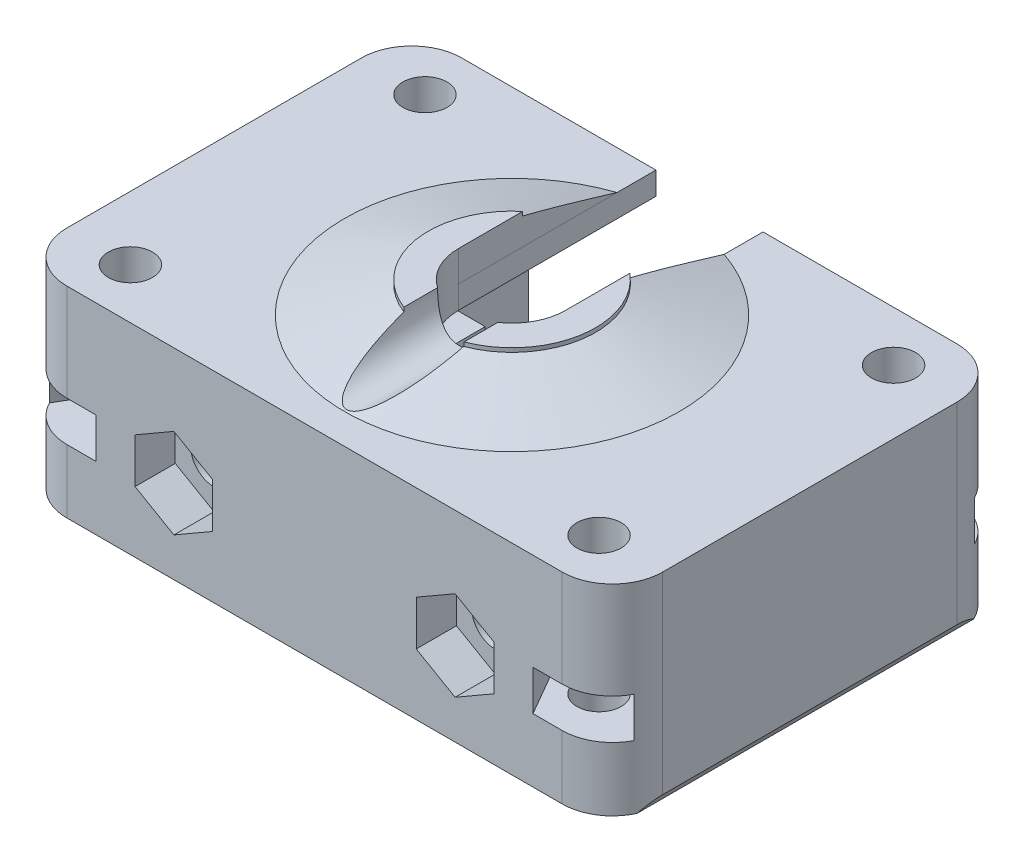
SolidWorks part; units mm, degrees
ref_plane "Plano frontal" through (0, 0, 0) normal (0, 0, 1) x (1, 0, 0)
ref_plane "Plano superior" through (0, 0, 0) normal (0, 1, 0) x (1, 0, 0)
ref_plane "Plano direito" through (0, 0, 0) normal (1, 0, 0) x (0, 0, -1)
sketch "Esboço1" plane through (0, 0, 0) normal (0, 1, 0) x (1, 0, 0)
  line L0 (-18.7321, -12.0975) -> (-21.3284, -13.8284) construction
  line L1 (-18.5, -15) -> (18.5, -15)
  line L2 (-22.5, -11) -> (-22.5, 11)
  line L3 (-18.5, 15) -> (18.5, 15)
  line L4 (22.5, -11) -> (22.5, 11)
  line L5 (-22.5, -15) -> (22.5, 15) construction
  line L6 (-22.5, 15) -> (22.5, -15) construction
  line L7 (-17.5, -11) -> (17.5, -11) construction
  line L8 (17.5, -11) -> (17.5, 11) construction
  line L9 (17.5, 11) -> (-17.5, 11) construction
  line L10 (-17.5, 11) -> (-17.5, -11) construction
  line L11 (0, -11) -> (0, 0) construction
  line L12 (-17.5, 0) -> (0, 0) construction
  arc A0 (-18.5, -15) -> (-22.5, -11) centre (-18.5, -11) cw
  arc A1 (18.5, -15) -> (22.5, -11) centre (18.5, -11) ccw
  arc A2 (18.5, 15) -> (22.5, 11) centre (18.5, 11) cw
  arc A3 (-22.5, 11) -> (-18.5, 15) centre (-18.5, 11) cw
  circle A8 centre (-17.5, -11) radius 1.65
  circle A9 centre (-17.5, 11) radius 1.65
  circle A10 centre (17.5, -11) radius 1.65
  circle A11 centre (17.5, 11) radius 1.65
  point P0 (0, 0)
  dimension "D3" = 4
  dimension "D4" = 35
  dimension "D6" = 3.3
  dimension "D1" = 45
  dimension "D2" = 30
  dimension "D5" = 22
extrude "Ressalto-extrusão1" add sketch "Esboço1" along normal blind 17
sketch "Esboço3" plane through (0, 0, 0) normal (0, -1, 0) x (1, 0, 0)
  line L0 (-4, -15) -> (4, -15)
  line L1 (4, -15) -> (4, 0)
  line L2 (-4, -15) -> (-4, 0)
  line L3 (18.5, -15) -> (-18.5, -15) construction
  line L4 (0, 0) -> (0, -15) construction
  arc A0 (-4, 0) -> (4, 0) centre (0, 0) cw
  dimension "D2" = 4
extrude "Corte-extrusão2" cut sketch "Esboço3" against normal through all
sketch "Esboço4" plane through (0, 0, 0) normal (0, -1, 0) x (1, 0, 0)
  line L0 (-8.48, -15) -> (-8.48, 0)
  line L1 (-6.25, -15) -> (-6.25, 0)
  line L2 (6.25, -15) -> (6.25, 0)
  line L3 (8.48, -15) -> (8.48, 0)
  line L4 (-8.48, -15) -> (8.48, -15)
  line L5 (0, -15) -> (0, 0) construction
  line L7 (18.5, -15) -> (4, -15) construction
  arc A0 (-8.48, 0) -> (8.48, 0) centre (0, 0) cw
  arc A1 (-6.25, 0) -> (6.25, 0) centre (0, 0) cw
  line M44 (-4, -15) -> (-4, 0)
  arc M45 (-4, 0) -> (4, 0) centre (0, 0) cw
  line M46 (4, 0) -> (4, -15)
  line M47 (4, -15) -> (18.5, -15)
  line M55 (-18.5, -15) -> (-4, -15)
  dimension "D1" = 8.48
  dimension "D2" = 6.25
extrude "Corte-extrusão3" cut sketch "Esboço4" against normal blind 5.5 contours A0 L3 L4 L0
extrude "Corte-extrusão4" cut sketch "Esboço4<3>" against normal blind 15.3 contours A1 L1 L2 M55 M44 M45 M46 M47 region at (-6.0035, 0, -7.5)
sketch "Esboço4<3>" plane through (0, 0, 0) normal (0, -1, 0) x (1, 0, 0) same geometry as "Esboço4"
sketch "Esboço5" plane through (0, 15.3, 0) normal (0, -1, 0) x (1, 0, 0)
  line L0 (-8.48, -15) -> (-8.48, 0.0526)
  line L1 (-6.25, -15) -> (-6.25, 0.0526)
  line L2 (6.25, -15) -> (6.25, 0.0526)
  line L3 (8.48, -15) -> (8.48, 0.0526)
  line L4 (-8.48, -15) -> (8.48, -15)
  line L5 (0, -15) -> (0, 0) construction
  line L6 (-6.25, -15) -> (-4, -15) construction
  line L7 (-6.25, 0) -> (-6.25, -15) construction
  arc A0 (-8.48, 0.0526) -> (8.48, 0.0526) centre (0, 0.0526) cw
  arc A1 (-6.25, 0.0526) -> (6.25, 0.0526) centre (0, 0.0526) cw
  dimension "D1" = 8.48
  dimension "D2" = 6.25
  dimension "D3" = 15.0526
extrude "Corte-extrusão5" cut sketch "Esboço5" along normal blind 4.3 contours L0 A0 L3 L4
sketch "Esboço6" plane through (0, 17, 0) normal (0, 1, 0) x (1, 0, 0)
  line L0 (-14, 0) -> (-14, 8.3)
  line L1 (14, 0) -> (14, 8.3)
  line L2 (14, 8.3) -> (-14, 8.3)
  line L3 (-4, 0) -> (-4, 8.3)
  line L4 (4, 0) -> (4, 8.3)
  circle A0 centre (0, 0) radius 4
  circle A1 centre (0, 0) radius 6.25
  arc A3 (-14, 0) -> (14, 0) centre (0, 0) ccw
  circle A4 centre (0, 0) radius 12.5
  arc A5 (-4, 0) -> (4, 0) centre (0, 0) ccw construction
  dimension "D1" = 8
  dimension "D2" = 12.5
  dimension "D3" = 25
  dimension "D4" = 28
  dimension "D5" = 8.3
ref_plane "Plano1" through (0, 19, 0) normal (0, 1, 0) x (1, 0, 0)
sketch "Esboço7" plane through (0, 19, 0) normal (0, 1, 0) x (1, 0, 0)
  line L0 (-14, 0) -> (-14, 8.3)
  line L1 (14, 0) -> (14, 8.3)
  line L2 (14, 8.3) -> (-14, 8.3)
  line L3 (-4, 0) -> (-4, 8.3)
  line L4 (4, 0) -> (4, 8.3)
  circle A0 centre (0, 0) radius 4
  circle A1 centre (0, 0) radius 6.25
  arc A3 (-14, 0) -> (14, 0) centre (0, 0) ccw
  circle A4 centre (0, 0) radius 11.25
  circle A6 centre (0, 0) radius 4 construction
  dimension "D1" = 8
  dimension "D2" = 12.5
  dimension "D3" = 22.5
  dimension "D4" = 28
  dimension "D5" = 8.3
loft "Loft1" add section "Esboço6" section "Esboço7" connector at (-5.022, 17, 11.4468) connector at (-2.3737, 19, 5.7817)
sketch "Esboço8" plane through (0, 19, 0) normal (0, 1, 0) x (1, 0, 0)
  circle A1 centre (0, 0) radius 6.25
  circle A2 centre (0, 0) radius 6.25
  dimension "D1" = 0
extrude "Ressalto-extrusão2" add sketch "Esboço8" along normal blind 0.3
sketch "Esboço9" plane through (0, 17, 0) normal (0, -1, 0) x (1, 0, 0)
  line L2 (-4, 0) -> (-4, -11.8428)
  line L3 (4, -11.8428) -> (4, 0)
  line L4 (-4, 0) -> (-4, -11.8428)
  line L5 (4, -11.8428) -> (4, 0)
  arc A1 (4, 0) -> (-4, 0) centre (0, 0) ccw
  arc A2 (-4, -11.8428) -> (4, -11.8428) centre (0, 0) ccw
  arc A3 (4, 0) -> (-4, 0) centre (0, 0) ccw
  arc A4 (-4, -11.8428) -> (4, -11.8428) centre (0, 0) ccw
  dimension "D1" = 0
extrude "Corte-extrusão6" cut sketch "Esboço9" against normal through all
sketch "Esboço10" plane through (0, 0, -15) normal (0, 0, -1) x (-1, 0, 0)
  line L0 (4, 19.3) -> (-4, 19.3) construction
  circle A0 centre (0, 19.3) radius 2.25
  dimension "D1" = 4.5
extrude "Corte-extrusão7" cut sketch "Esboço10" against normal through all both and the other way through all
sketch "Esboço17" plane through (0, 0, 0) normal (0, -1, 0) x (1, 0, 0)
  line L0 (8.48, -14.75) -> (18.5, -14.75)
  line L1 (22.25, -11) -> (22.25, 11)
  line L2 (18.5, 14.75) -> (-18.5, 14.75)
  line L3 (-22.25, 11) -> (-22.25, -11)
  line L4 (-18.5, -14.75) -> (-8.48, -14.75)
  line L5 (-8.48, -14.75) -> (8.48, -14.75)
  line L6 (-8.48, -15) -> (8.48, -15)
  line L14 (-18.5, -15) -> (-8.48, -15)
  line L15 (-8.48, -15) -> (-8.48, 0)
  line L16 (8.48, 0) -> (8.48, -15)
  line L17 (8.48, -15) -> (18.5, -15)
  line L18 (22.5, -11) -> (22.5, 11)
  line L19 (18.5, 15) -> (-18.5, 15)
  line L20 (-22.5, 11) -> (-22.5, -11)
  line L21 (-18.5, -15) -> (-8.48, -15)
  line L24 (8.48, -15) -> (18.5, -15)
  line L25 (22.5, -11) -> (22.5, 11)
  line L26 (18.5, 15) -> (-18.5, 15)
  line L27 (-22.5, 11) -> (-22.5, -11)
  arc A0 (18.5, -14.75) -> (22.25, -11) centre (18.5, -11) ccw
  arc A1 (22.25, 11) -> (18.5, 14.75) centre (18.5, 11) ccw
  arc A2 (-18.5, 14.75) -> (-22.25, 11) centre (-18.5, 11) ccw
  arc A3 (-22.25, -11) -> (-18.5, -14.75) centre (-18.5, -11) ccw
  arc A10 (8.48, 0) -> (-8.48, 0) centre (0, 0) ccw
  arc A11 (18.5, -15) -> (22.5, -11) centre (18.5, -11) ccw
  arc A12 (22.5, 11) -> (18.5, 15) centre (18.5, 11) ccw
  arc A13 (-18.5, 15) -> (-22.5, 11) centre (-18.5, 11) ccw
  arc A14 (-22.5, -11) -> (-18.5, -15) centre (-18.5, -11) ccw
  arc A16 (18.5, -15) -> (22.5, -11) centre (18.5, -11) ccw
  arc A17 (22.5, 11) -> (18.5, 15) centre (18.5, 11) ccw
  arc A18 (-18.5, 15) -> (-22.5, 11) centre (-18.5, 11) ccw
  arc A19 (-22.5, -11) -> (-18.5, -15) centre (-18.5, -11) ccw
  dimension "D1" = 0
  dimension "D2" = 0.25
extrude "Corte-extrusão14" cut sketch "Esboço17" against normal through all both and the other way through all
sketch "Esboço20" plane through (0, 0, 14.75) normal (0, 0, 1) x (1, 0, 0)
  line L0 (-20.75, 0) -> (-22.25, 2.5981)
  line L1 (-22.25, 17) -> (-22.25, 0) construction
  line L2 (-22.25, 2.5981) -> (-22.25, 0)
  line L3 (-22.25, 0) -> (-20.75, 0)
  line L4 (20.75, 0) -> (22.25, 2.5981)
  line L5 (22.25, 17) -> (22.25, 0) construction
  line L6 (22.25, 2.5981) -> (22.25, 0)
  line L7 (22.25, 0) -> (20.75, 0)
  dimension "D1" = 60
  dimension "D2" = 60
  dimension "D3" = 1.5
extrude "Corte-extrusão17" cut sketch "Esboço20" against normal through all both and the other way through all
ref_plane "Plano2" through (0, 8.25, 0) normal (0, 1, 0) x (1, 0, 0)
sketch "Esboço21" plane through (0, 8.25, 0) normal (0, 1, 0) x (1, 0, 0)
  line L0 (-20.8486, 11) -> (-26.3667, 20.5576)
  line L1 (-19.1743, 8.1) -> (-15.8257, 8.1)
  line L2 (-15.8257, 8.1) -> (-14.1514, 11)
  line L3 (-14.1514, 11) -> (-15.8257, 13.9)
  line L4 (-15.8257, 13.9) -> (-19.1743, 13.9) construction
  line L5 (-19.1743, 13.9) -> (-20.8486, 11) construction
  line L6 (-20.8486, 11) -> (-19.1743, 8.1)
  line L7 (19.1743, 8.1) -> (20.8486, 11)
  line L8 (20.8486, 11) -> (19.1743, 13.9) construction
  line L9 (19.1743, 13.9) -> (15.8257, 13.9) construction
  line L10 (15.8257, 13.9) -> (14.1514, 11)
  line L11 (14.1514, 11) -> (15.8257, 8.1)
  line L12 (15.8257, 8.1) -> (19.1743, 8.1)
  line L13 (15.8257, -8.1) -> (14.1514, -11)
  line L14 (14.1514, -11) -> (15.8257, -13.9)
  line L15 (15.8257, -13.9) -> (19.1743, -13.9) construction
  line L16 (19.1743, -13.9) -> (20.8486, -11) construction
  line L17 (20.8486, -11) -> (19.1743, -8.1)
  line L18 (19.1743, -8.1) -> (15.8257, -8.1)
  line L19 (-19.1743, -8.1) -> (-20.8486, -11)
  line L20 (-20.8486, -11) -> (-19.1743, -13.9) construction
  line L21 (-19.1743, -13.9) -> (-15.8257, -13.9) construction
  line L22 (-15.8257, -13.9) -> (-14.1514, -11)
  line L23 (-14.1514, -11) -> (-15.8257, -8.1)
  line L24 (-15.8257, -8.1) -> (-19.1743, -8.1)
  line L25 (-26.3667, 20.5576) -> (-21.3438, 23.4576)
  line L26 (-21.3438, 23.4576) -> (-15.8257, 13.9)
  line L27 (15.8257, 13.9) -> (21.1585, 23.1367)
  line L28 (20.8486, 11) -> (26.0852, 20.07)
  line L29 (26.0852, 20.07) -> (21.1585, 23.1367)
  line L30 (20.8486, -11) -> (25.5133, -19.0794)
  line L31 (15.8257, -13.9) -> (19.679, -20.5741)
  line L32 (19.679, -20.5741) -> (25.5133, -19.0794)
  line L33 (-20.8486, -11) -> (-25.4451, -18.9613)
  line L34 (-15.8257, -13.9) -> (-20.0503, -21.2173)
  line L35 (-25.4451, -18.9613) -> (-20.0503, -21.2173)
  circle A0 centre (-17.5, 11) radius 2.9 construction
  circle A1 centre (17.5, 11) radius 2.9 construction
  circle A2 centre (17.5, -11) radius 2.9 construction
  circle A3 centre (-17.5, -11) radius 2.9 construction
  point P38 (0, 0)
  point P45 (-27.1361, 20.07)
  dimension "D1" = 5.8
extrude "Corte-extrusão18" cut sketch "Esboço21" against normal mid plane 3
sketch "Esboço22" plane through (0, 0, 0) normal (0, -1, 0) x (1, 0, 0)
  line L1 (-36.7657, 14.8012) -> (36.7657, 14.8012)
  line L2 (-36.7657, 14.8012) -> (-36.7657, -14.8012)
  line L3 (-36.7657, -14.8012) -> (36.7657, -14.8012)
  line L4 (36.7657, 14.8012) -> (36.7657, -14.8012)
  line L5 (-36.7657, 14.8012) -> (36.7657, -14.8012) construction
  line L6 (-36.7657, -14.8012) -> (36.7657, 14.8012) construction
  point P0 (0, 0)
extrude "Corte-extrusão19" cut sketch "Esboço22" against normal blind 2
sketch "Esboço27" plane through (0, 0, -14.75) normal (0, 0, -1) x (-1, 0, 0)
  line L0 (-16.3164, 8.25) -> (16.3164, 8.25) construction
  line L1 (-16.3164, 6.75) -> (-16.3164, 9.75) construction
  line L2 (16.3164, 9.75) -> (16.3164, 6.75) construction
  line L3 (0, 0) -> (0, 23.2516) construction
  circle A0 centre (-10.5, 8.25) radius 1.75
  circle A1 centre (10.5, 8.25) radius 1.75
  dimension "D1" = 10.5
  dimension "D2" = 3.5
sketch "Esboço28" plane through (0, 0, -14.75) normal (0, 0, -1) x (-1, 0, 0)
  line L0 (-13.5, 2) -> (-13.5, 15.3)
  line L1 (-18.5, 2) -> (-8.48, 2) construction
  line L2 (-13.5, 15.3) -> (13.5, 15.3)
  line L3 (13.5, 15.3) -> (13.5, 2)
  line L4 (8.48, 2) -> (18.5, 2) construction
  line L5 (13.5, 2) -> (-13.5, 2)
  line L6 (0, 0) -> (0, 15.3) construction
  line L7 (-8.48, 15.3) -> (8.48, 15.3) construction
  dimension "D1" = 27
extrude "Corte-extrusão22" cut sketch "Esboço28" against normal blind 10.5
extrude "Corte-extrusão23" cut sketch "Esboço27" against normal through all
sketch "Esboço29" plane through (0, 0, 14.75) normal (0, 0, 1) x (1, 0, 0)
  line L0 (9.328, 8.25) -> (-9.328, 8.25) construction
  line L1 (-7.6, 9.9243) -> (-10.5, 11.5986)
  line L2 (-10.5, 11.5986) -> (-13.4, 9.9243)
  line L3 (-13.4, 9.9243) -> (-13.4, 6.5757)
  line L4 (-13.4, 6.5757) -> (-10.5, 4.9014)
  line L5 (-10.5, 4.9014) -> (-7.6, 6.5757)
  line L6 (-7.6, 6.5757) -> (-7.6, 9.9243)
  line L8 (10.5, 11.5986) -> (7.6, 9.9243)
  line L9 (7.6, 9.9243) -> (7.6, 6.5757)
  line L10 (7.6, 6.5757) -> (10.5, 4.9014)
  line L11 (10.5, 4.9014) -> (13.4, 6.5757)
  line L12 (13.4, 6.5757) -> (13.4, 9.9243)
  line L13 (13.4, 9.9243) -> (10.5, 11.5986)
  circle A0 centre (-10.5, 8.25) radius 2.9 construction
  circle A1 centre (10.5, 8.25) radius 2.9 construction
  dimension "D1" = 5.8
extrude "Corte-extrusão24" cut sketch "Esboço29" against normal blind 3
sketch "Esboço23" plane through (0, 8.25, 0) normal (0, 1, 0) x (1, 0, 0)
  line L0 (0, 0) -> (-22.25, 8.9896)
  line L2 (-22.25, -11) -> (-22.25, 11) construction
  line L3 (0, 0) -> (-16.5576, 0) construction
  circle A0 centre (0, 0) radius 6.25 construction
  dimension "D1" = 12.5
  dimension "D2" = 22
